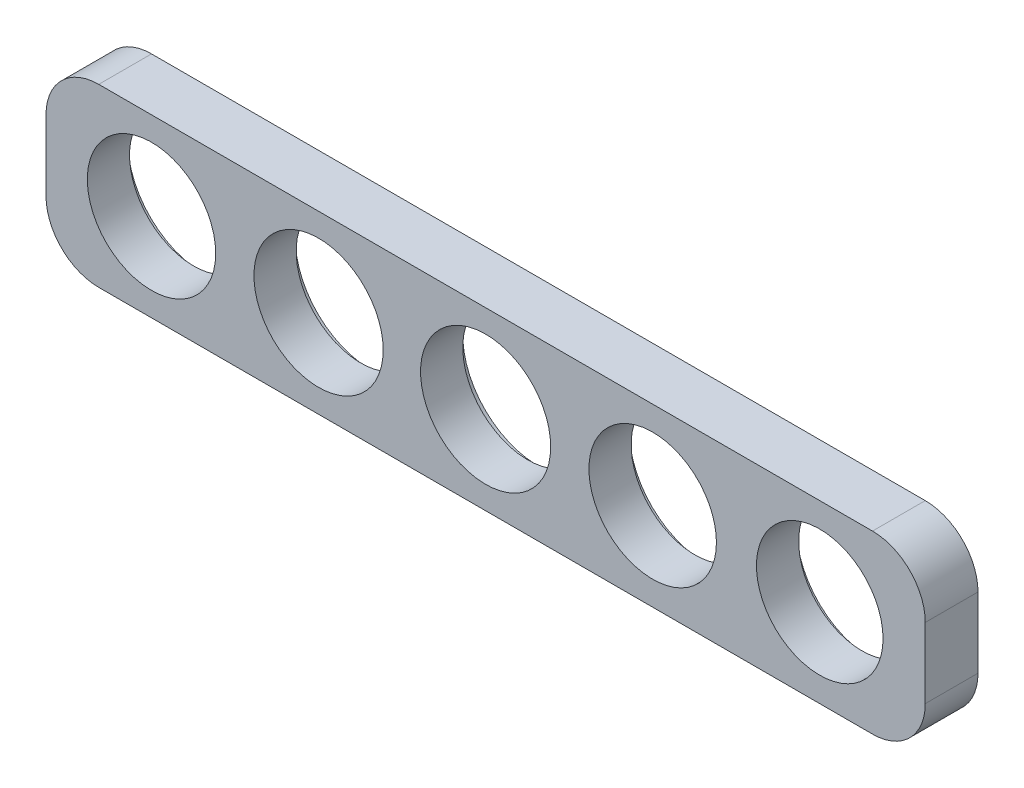
SolidWorks part; units mm, degrees
ref_plane "前视基准面" through (0, 0, 0) normal (0, 0, 1) x (1, 0, 0)
ref_plane "上视基准面" through (0, 0, 0) normal (0, 1, 0) x (1, 0, 0)
ref_plane "右视基准面" through (0, 0, 0) normal (1, 0, 0) x (0, 0, -1)
sketch "草图1" plane through (0, 0, 0) normal (0, 0, 1) x (1, 0, 0)
  line L0 (-50, 5) -> (0, 5) construction
  line L1 (-50, 10) -> (0, 10)
  line L2 (-50, 10) -> (-50, 0)
  line L3 (-50, 0) -> (0, 0)
  line L4 (0, 10) -> (0, 0)
  line L5 (-50, 10) -> (0, 0) construction
  line L6 (-50, 0) -> (0, 10) construction
  circle A0 centre (-44, 5) radius 3.65
  circle A2 centre (-44, 5) radius 4.35
  circle A3 centre (-34.5, 5) radius 3.675
  circle A4 centre (-34.5, 5) radius 4.325
  circle A5 centre (-25, 5) radius 3.7
  circle A6 centre (-25, 5) radius 4.3
  circle A7 centre (-15.5, 5) radius 3.625
  circle A8 centre (-15.5, 5) radius 4.325
  circle A9 centre (-6, 5) radius 3.6
  circle A10 centre (-6, 5) radius 4.325
  point P0 (-25, 5)
  dimension "D3" = 7.3
  dimension "D4" = 8.7
  dimension "D5" = 9.5
  dimension "D9" = 7.35
  dimension "D10" = 7.4
  dimension "D11" = 7.25
  dimension "D12" = 7.2
  dimension "D13" = 8.65
  dimension "D14" = 8.6
  dimension "D15" = 8.65
  dimension "D16" = 8.65
  dimension "D1" = 10
  dimension "D2" = 50
  dimension "D6" = 9.5
  dimension "D7" = 9.5
  dimension "D8" = 9.5
extrude "凸台-拉伸1" add sketch "草图1" along normal blind 3 contours L1 L4 L3 L2
extrude "切除-拉伸1" cut sketch "草图1<3>" along normal through all contours A5 | A3 | A0 | A9 | A7 region at (-44, 5, 0) region at (-34.5, 5, 0) region at (-25, 5, 0)
sketch "草图1<3>" plane through (0, 0, 0) normal (0, 0, 1) x (1, 0, 0) same geometry as "草图1"
extrude "切除-拉伸2" cut sketch "草图1<4>" along normal blind 0.6 contours A6 A5 | A2 A0 | A4 A3 | A8 A7 | A10 A9 region at (-48.227, 5, 0) region at (-38.7027, 5, 0) region at (-29.1784, 5, 0) region at (-19.7027, 5, 0) region at (-10.2027, 5, 0)
sketch "草图1<4>" plane through (0, 0, 0) normal (0, 0, 1) x (1, 0, 0) same geometry as "草图1"
fillet "圆角4" radius 3 4 edges at (-50, 10, 1.5) (-50, 0, 1.5) (0, 10, 1.5) (0, 0, 1.5)
